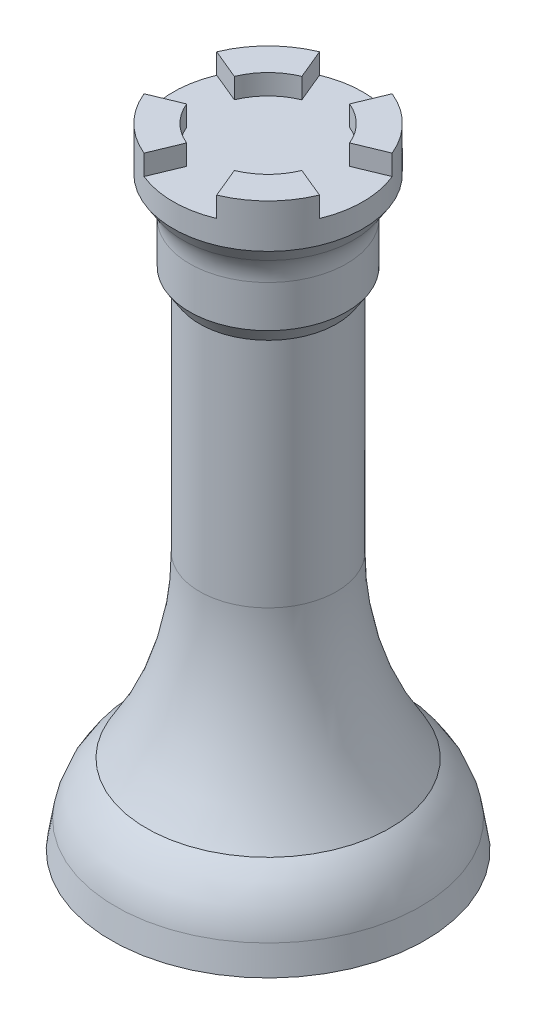
SolidWorks part; units mm, degrees
ref_plane "Front Plane" through (0, 0, 0) normal (0, 0, 1) x (1, 0, 0)
ref_plane "Top Plane" through (0, 0, 0) normal (0, 1, 0) x (1, 0, 0)
ref_plane "Right Plane" through (0, 0, 0) normal (1, 0, 0) x (0, 0, -1)
sketch "Sketch1" plane through (0, 0, 0) normal (0, 0, 1) x (1, 0, 0)
  line L21 (4.5897, -9.2849) -> (-7.0103, -9.2849)
  line L22 (-6.678, -7.2849) -> (-7.0103, -9.2849)
  line L23 (4.5897, 35.7151) -> (4.5897, -9.2849)
  line L25 (4.5897, -9.2849) -> (4.5897, 40.7151) construction
  line L26 (-1.2092, 28.0478) -> (-0.4727, 26.9092)
  line L27 (-0.0203, 35.7151) -> (4.5897, 35.7151)
  line L28 (-0.4727, 26.9092) -> (-0.4727, 9.7789)
  line L29 (-0.0203, 35.7151) -> (-0.0203, 37.2151)
  line L30 (-0.0203, 37.2151) -> (-2.4303, 37.2151)
  line L33 (-2.4303, 33.9851) -> (-1.735, 32.9104)
  line L34 (-1.2092, 31.1297) -> (-1.2092, 28.0478)
  line L36 (-2.4303, 33.9851) -> (-2.4303, 35.7151)
  line L37 (-2.4303, 37.2151) -> (-2.4303, 35.7151)
  line L38 (-0.0203, 35.7151) -> (-2.4303, 35.7151)
  arc A6 (-4.4103, -3.4011) -> (-6.678, -7.2849) centre (-0.4448, -8.3205) ccw
  arc A8 (-1.735, 32.9104) -> (-1.2092, 31.1297) centre (-4.4875, 31.1297) cw
  arc A9 (-0.4727, 9.7789) -> (-4.4103, -3.4011) centre (-24.4993, 9.7789) cw
  dimension "D6" = 11.6
  dimension "D11" = 6.3187
  dimension "D14" = 4.61
  dimension "D18" = 3.23
  dimension "D22" = 3.2783
  dimension "D2" = 2
  dimension "D3" = 1.5
  dimension "D7" = 45
  dimension "D8" = 5.8838
  dimension "D12" = 9
  dimension "D16" = 2.41
  dimension "D17" = 1.28
  dimension "D21" = 5.7989
revolve "Revolve5" add sketch "Sketch1" angle 360 about L25 region at (1.1021, 10.7577, 0) region at (-1.2253, 36.4651, 0)
revolve "Cut-Revolve1" cut sketch "Sketch1<3>" angle 45 mid plane about L25 region at (-1.2253, 36.4651, 0)
sketch "Sketch1<3>" plane through (0, 0, 0) normal (0, 0, 1) x (1, 0, 0) same geometry as "Sketch1"
pattern_circular "CirPattern1" count 4 every 90 about axis through (4.5897, -9.2849, 0) along (0, 1, 0) of "Cut-Revolve1"
sketch "Sketch2" plane through (0, -9.2849, 0) normal (0, -1, 0) x (1, 0, 0)
  circle A0 centre (4.5897, 0) radius 10
extrude "Cut-Extrude1" cut sketch "Sketch2" against normal blind 2 from offset 0.4 offset against normal yes
